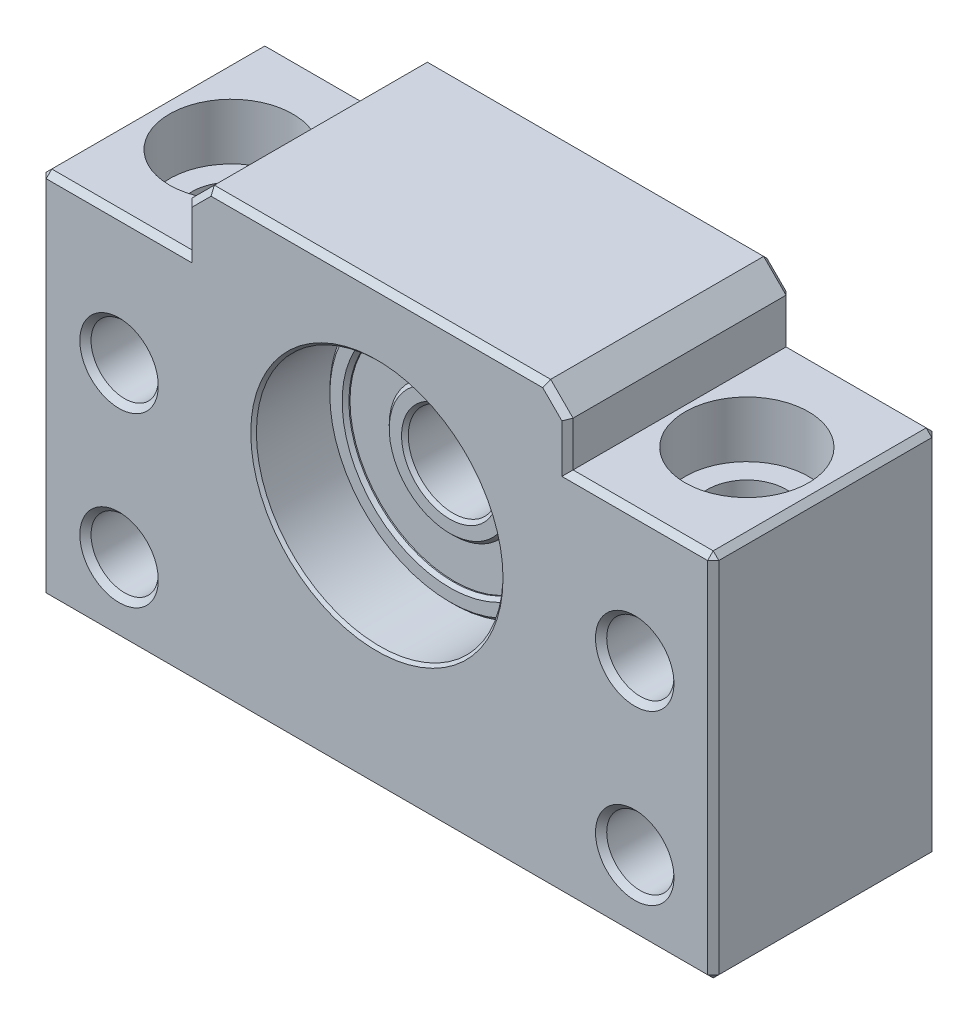
SolidWorks part; units mm, degrees
ref_plane "Front" through (0, 0, 0) normal (0, 0, 1) x (1, 0, 0)
ref_plane "Top" through (0, 0, 0) normal (0, 1, 0) x (1, 0, 0)
ref_plane "Right" through (0, 0, 0) normal (1, 0, 0) x (0, 0, -1)
sketch "Sketch1" plane through (0, 0, 0) normal (0, 0, 1) x (1, 0, 0)
  line L0 (0, 17) -> (0, -22) construction
  line L1 (-17, 17) -> (17, 17)
  line L2 (-17, 17) -> (-17, 11)
  line L3 (17, 11) -> (30, 11)
  line L4 (17, 17) -> (17, 11)
  line L7 (-30, 11) -> (-17, 11)
  line L8 (-30, 11) -> (-30, -22)
  line L9 (-30, -22) -> (30, -22)
  line L10 (30, 11) -> (30, -22)
  circle A0 centre (0, 0) radius 11 construction
  point P0 (0, 0)
  dimension "D6" = 22
  dimension "D1" = 34
  dimension "D2" = 60
  dimension "D3" = 33
  dimension "D4" = 39
  dimension "D5" = 22
extrude "Boss-Extrude1" add sketch "Sketch1" along normal blind 10 and the other way blind 10
chamfer "Chamfer1" distance 2 angle 45 2 edges at (-17, 17, 0) (17, 17, 0)
hole_wizard "hole 22mm bearing" positions "Sketch5" profile "Sketch6" hole size "Ø4.0" standard "ISO" end condition through all
sketch "Sketch5" plane through (0, 0, -10) normal (0, 0, -1) x (-1, 0, 0)
  point P0 (0, 0)
sketch "Sketch6" plane through (0, 0, -10) normal (1, 0, 0) x (0, 1, 0)
  line L0 (0, 0) -> (0, 20)
  line L1 (0, 20) -> (11.25, 20)
  line L2 (11, 19.75) -> (11, 0.25)
  line L3 (11, 0.25) -> (11.25, 0)
  line L5 (11.25, 0) -> (0, 0)
  line L6 (-11, 0.25) -> (-11.25, 0) construction
  line L7 (11.25, 20) -> (11, 19.75)
  line L8 (-11.25, 20) -> (-11, 19.75) construction
  line L11 (0, -6.35) -> (0, 107.95) construction
  dimension "Thru Hole Dia." = 22
  dimension "Thru Hole Depth" = 20
  dimension "Near C'Sink Dia." = 22.5
  dimension "Near C'Sink Angle" = 90
  dimension "Far C'Sink Dia." = 22.5
  dimension "Far C'Sink Angle" = 90
hole_wizard "hole 6mm mount front" positions "Sketch8" profile "Sketch7" hole size "Ø6.0" standard "ISO" end condition up to next
sketch "Sketch8" plane through (0, 0, -10) normal (0, 0, -1) x (-1, 0, 0)
  line L1 (0, 0) -> (0, -22) construction
  line L2 (30, -22) -> (-30, -22) construction
  point P0 (-23, -0.5)
  point P2 (-23, -15.5)
  point P18 (23, -15.5)
  point P19 (23, -0.5)
  dimension "D1" = 46
  dimension "D2" = 6.5
  dimension "D3" = 15
sketch "Sketch7" plane through (23, -0.5, -10) normal (1, 0, 0) x (0, 1, 0)
  line L0 (0, 0) -> (0, 20)
  line L1 (0, 20) -> (3.5, 20)
  line L2 (3, 19.5) -> (3, 0.5)
  line L3 (3, 0.5) -> (3.5, 0)
  line L5 (3.5, 0) -> (0, 0)
  line L6 (-3, 0.5) -> (-3.5, 0) construction
  line L7 (3.5, 20) -> (3, 19.5)
  line L8 (-3.5, 20) -> (-3, 19.5) construction
  line L11 (0, -6.35) -> (0, 107.95) construction
  dimension "Thru Hole Dia." = 6
  dimension "Thru Hole Depth" = 20
  dimension "Near C'Sink Dia." = 7
  dimension "Near C'Sink Angle" = 90
  dimension "Far C'Sink Dia." = 7
  dimension "Far C'Sink Angle" = 90
hole_wizard "holes cap" positions "Sketch10" profile "Sketch11" counterbore size "M5" standard "ANSI Metric" end condition through all
sketch "Sketch10" plane through (0, 11, 0) normal (0, 1, 0) x (1, 0, 0)
  line L0 (0, 0) -> (0, -10) construction
  line L3 (-30, 0) -> (30, 0) construction
  line L4 (-30, -10) -> (-30, 10) construction
  line L5 (30, -10) -> (30, 10) construction
  line L6 (-11.25, -10) -> (11.25, -10) construction
  point P0 (23, 0)
  point P11 (-23, 0)
  dimension "D1" = 46
sketch "Sketch11" plane through (23, 11, 0) normal (1, 0, 0) x (0, 0, 1)
  line L0 (0, 0) -> (0, 33)
  line L1 (3.5, 32.5) -> (4, 33)
  line L2 (3.5, 32.5) -> (3.5, 5)
  line L3 (3.5, 5) -> (5.5, 5)
  line L4 (5.5, 5) -> (5.5, 0)
  line L5 (5.5, 0) -> (0, 0)
  line L11 (0, -6.35) -> (0, 107.95) construction
  line L12 (4, 33) -> (0, 33)
  line L13 (-3.5, 32.5) -> (-4, 33) construction
  dimension "Thru Hole Dia." = 7
  dimension "Thru Hole Depth" = 33
  dimension "C'Bore Dia." = 11
  dimension "C'Bore Depth" = 5
  dimension "Far C'Sink Dia." = 8
  dimension "Far C'Sink Angle" = 90
sketch "Sketch17" plane through (0, 0, 0) normal (0, 1, 0) x (1, 0, 0)
  line L0 (0, 10) -> (0, -10) construction
  line L1 (-5.7, 3.5) -> (-4, 3.5)
  line L2 (-5.7, 3.5) -> (-5.7, 3.1)
  line L3 (-5.7, -3.5) -> (-4, -3.5)
  line L4 (-4, 3.5) -> (-4, -3.5)
  line L5 (-9.3, 3.1) -> (-5.7, 3.1)
  line L7 (-9.3, 3.5) -> (-11, 3.5)
  line L8 (-9.3, 3.5) -> (-9.3, 3.1)
  line L9 (-9.3, -3.5) -> (-11, -3.5)
  line L10 (-11, 3.5) -> (-11, -3.5)
  line L11 (-9.3, -3.1) -> (-5.7, -3.1)
  line L12 (-11, 0) -> (-4, 0) construction
  line L13 (-9.3, -3.1) -> (-9.3, -3.5)
  line L14 (-5.7, -3.1) -> (-5.7, -3.5)
  line L15 (15, 10) -> (-15, 10) construction
  line L16 (15, -10) -> (-15, -10) construction
  point P9 (0, 0)
  point P10 (-4, 0)
  dimension "D1" = 7
  dimension "D2" = 8
  dimension "D3" = 1.7
  dimension "D4" = 1.7
  dimension "D5" = 0.4
  dimension "D6" = 22
revolve "Revolve2" add sketch "Sketch17" angle 360 about L0
chamfer "Chamfer4" distance 0.3 6 edges at (-4, 0, -3.5) (-5.7, 0, -3.5) (-4, 0, 3.5) (-5.7, 0, 3.5) (-11, 0, 3.5) (-9.3, 0, 3.5)
chamfer "Chamfer6" distance 0.5 24 edges at (-16, 16, 10) (23.5, 11, 10) (0, -22, 10) (-23.5, 11, 10) (30, -22, 0) (30, -5.5, 10) (30, 11, 0) (30, -5.5, -10) (-30, 11, 0) (-30, -5.5, 10) (-30, -22, 0) (0, -22, -10) (-30, -5.5, -10) (23.5, 11, -10) (17, 13, -10) (16, 16, -10) (0, 17, -10) (-16, 16, -10) (-17, 13, -10) (-23.5, 11, -10) (16, 16, 10) (17, 13, 10) (0, 17, 10) (-17, 13, 10)
sketch3d "3DSketch1"
  line L0 (-23, -21.5, 0) -> (-23, 6, 0) construction
  line L1 (-23, -22, 0) -> (-23, -21.5, 0) construction
  line L2 (23, -21.5, 0) -> (23, 6, 0) construction
  line L3 (23, -22, 0) -> (23, -21.5, 0) construction
  point P0 (-23, -32, 0)
  point P1 (23, -32, 0)
  dimension "D1" = 10
